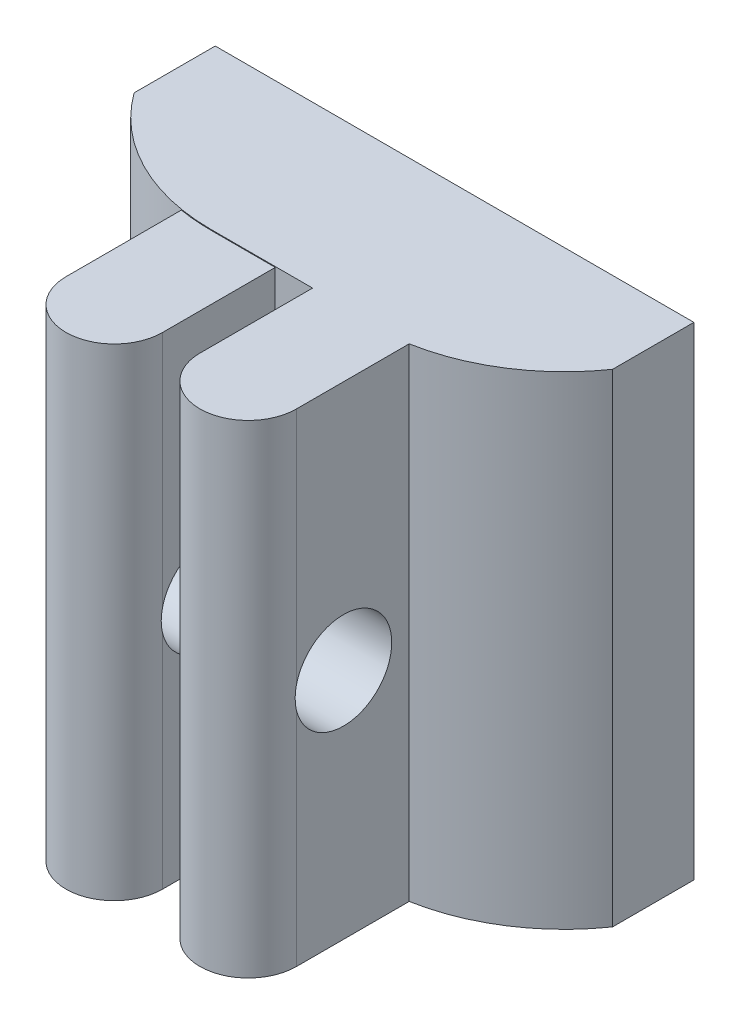
SolidWorks part; units mm, degrees
ref_plane "Front Plane" through (0, 0, 0) normal (0, 0, 1) x (1, 0, 0)
ref_plane "Top Plane" through (0, 0, 0) normal (0, 1, 0) x (1, 0, 0)
ref_plane "Right Plane" through (0, 0, 0) normal (1, 0, 0) x (0, 0, -1)
sketch "Sketch1" plane through (0, 0, 0) normal (0, 0, 1) x (1, 0, 0)
  line L1 (0, 0) -> (-17, 0)
  line L2 (0, 0) -> (0, -15)
  line L3 (0, -15) -> (-17, -15)
  line L4 (-17, 0) -> (-17, -15)
  dimension "D1" = 15
  dimension "D2" = 17
extrude "Boss-Extrude1" add sketch "Sketch1" along normal blind 5
sketch "Sketch2" plane through (0, 0, 5) normal (0, 0, 1) x (1, 0, 0)
  line L0 (0, 0) -> (-17, 0) construction
  line L1 (-7.92, 0) -> (-4.92, 0)
  line L2 (-7.92, 0) -> (-7.92, -15)
  line L3 (-7.92, -15) -> (-4.92, -15)
  line L4 (-4.92, 0) -> (-4.92, -15)
  line L5 (-17, -15) -> (0, -15) construction
  line L7 (-8.5, 0) -> (-8.5, -15) construction
  line L8 (-12.08, -0.0236) -> (-9.08, -0.0236)
  line L9 (-12.08, -0.0236) -> (-12.08, -15)
  line L10 (-12.08, -15) -> (-9.08, -15)
  line L11 (-9.08, -0.0236) -> (-9.08, -15)
  dimension "D1" = 4.92
  dimension "D2" = 3
  dimension "D3" = 4.92
extrude "Boss-Extrude2" add sketch "Sketch2" along normal blind 5
sketch "Sketch4" plane through (-9.08, 0, 0) normal (1, 0, 0) x (0, 0, -1)
  circle A0 centre (-7.0414, -7.7625) radius 1.5
  dimension "D1" = 3
extrude "Cut-Extrude2" cut sketch "Sketch4" against normal through all both and the other way through all
fillet "Fillet1" radius 6 2 edges at (-17, -7.5, 5) (0, -7.5, 5)
fillet "Fillet3" 2 edges at (-12.08, -7.5118, 10) (-9.08, -7.5118, 10) type full round first side face at (-12.08, -6.2625, 7.0414) second side face at (-9.08, -9.2625, 7.0414) middle face at (-10.58, -7.5118, 10)
fillet "Fillet4" 2 edges at (-7.92, -7.5, 10) (-4.92, -7.5, 10) type full round first side face at (-7.92, -6.2625, 7.0414) second side face at (-4.92, -9.2625, 7.0414) middle face at (-6.42, -7.5, 10)
sketch "Sketch5" plane through (0, 0, 0) normal (0, 0, 1) x (1, 0, 0)
  line L0 (-4.92, -15) -> (-0.0682, -15) construction
  line L1 (-0.0682, 0) -> (-1.0762, 0)
  line L2 (-0.0682, 0) -> (-0.0682, -15)
  line L3 (-0.0682, -15) -> (-1.0762, -15)
  line L4 (-1.0762, 0) -> (-1.0762, -15)
  line L5 (-17, -15) -> (-12.08, -15) construction
  line L6 (-17, 0) -> (-15.9436, 0)
  line L7 (-17, 0) -> (-17, -15)
  line L8 (-17, -15) -> (-15.9436, -15)
  line L9 (-15.9436, 0) -> (-15.9436, -15)
extrude "Cut-Extrude4" cut sketch "Sketch5" along normal blind 10
